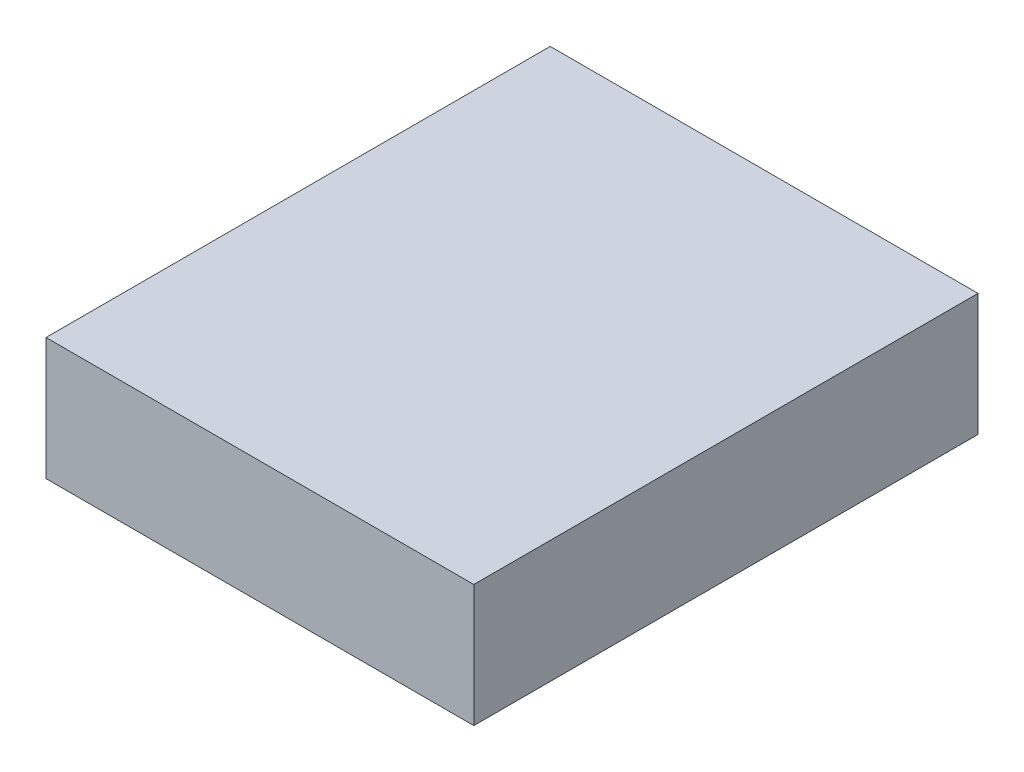
SolidWorks part; units mm, degrees
ref_plane "Front Plane" through (0, 0, 0) normal (0, 0, 1) x (1, 0, 0)
ref_plane "Top Plane" through (0, 0, 0) normal (0, 1, 0) x (1, 0, 0)
ref_plane "Right Plane" through (0, 0, 0) normal (1, 0, 0) x (0, 0, -1)
sketch "Sketch1" plane through (0, 0, 0) normal (0, 1, 0) x (1, 0, 0)
  line L1 (35, -41.25) -> (-35, -41.25)
  line L2 (35, -41.25) -> (35, 41.25)
  line L3 (35, 41.25) -> (-35, 41.25)
  line L4 (-35, -41.25) -> (-35, 41.25)
  line L5 (35, -41.25) -> (-35, 41.25) construction
  line L6 (35, 41.25) -> (-35, -41.25) construction
  point P0 (0, 0)
  dimension "D1" = 70
  dimension "D2" = 82.5
extrude "Boss-Extrude1" add sketch "Sketch1" along normal blind 20
